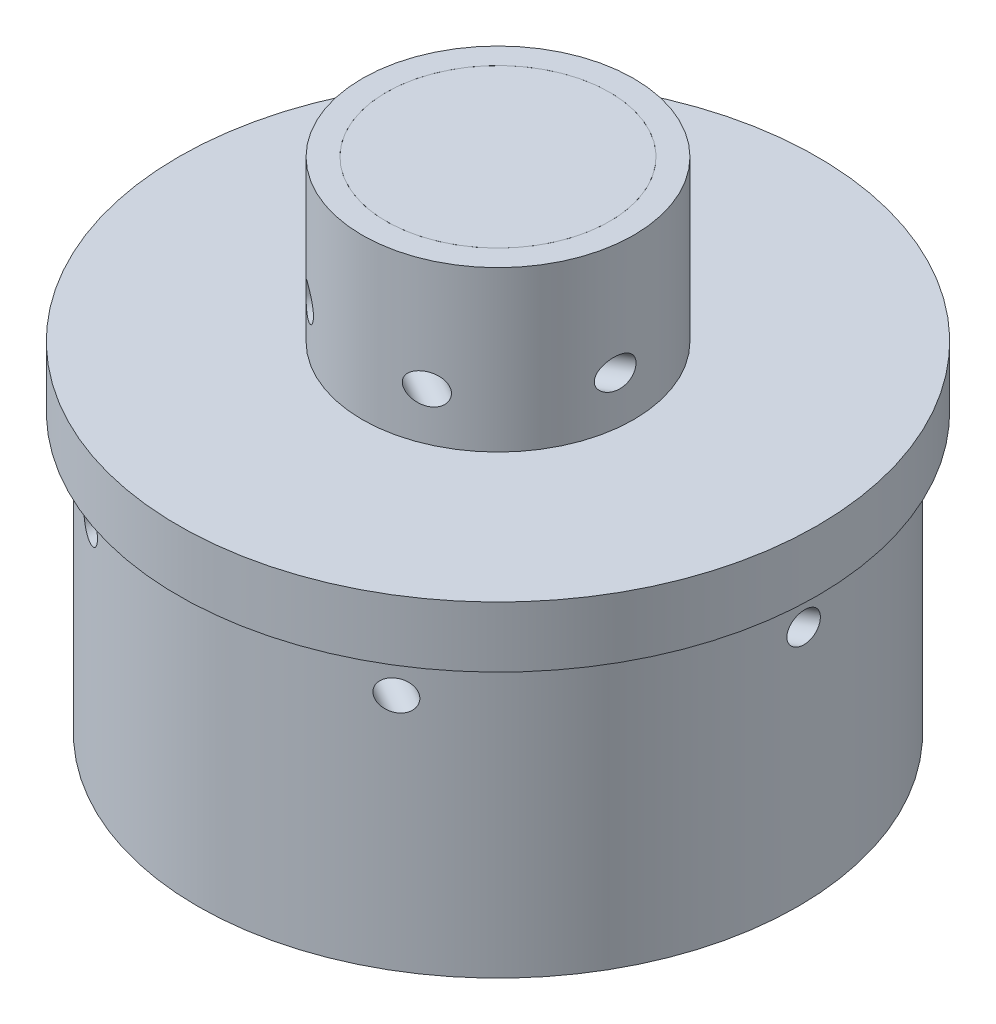
SolidWorks part; units mm, degrees
material "ASTM A36 Steel"
ref_plane "Front Plane" through (0, 0, 0) normal (0, 0, 1) x (1, 0, 0)
ref_plane "Top Plane" through (0, 0, 0) normal (0, 1, 0) x (1, 0, 0)
ref_plane "Right Plane" through (0, 0, 0) normal (1, 0, 0) x (0, 0, -1)
ref_axis "Axis1" through (0, 42.935, 0) along (0, -1, 0)
sketch "Sketch1" plane through (0, 0, 0) normal (0, 0, 1) x (1, 0, 0)
  line L1 (-5.3975, 0) -> (-5.3975, -6.35)
  line L2 (-5.3975, -6.35) -> (-12.7, -6.35)
  line L3 (-12.7, -6.35) -> (-12.7, -8.763)
  line L7 (-3.81, -3.175) -> (-3.81, -14.605)
  line L8 (-3.81, -14.605) -> (-2.54, -15.1311)
  line L9 (-2.54, -15.1311) -> (-2.54, -17.6711)
  line L10 (-2.54, -17.6711) -> (-3.3337, -17.6711)
  line L11 (-3.3337, -17.6711) -> (-3.3337, -15.6614)
  line L12 (-3.3337, -15.6614) -> (-4.6037, -15.1354)
  line L13 (-4.6037, -15.1354) -> (-4.6037, -9.525)
  line L14 (0, -1.5875) -> (0, -17.8202) construction
  line L15 (-4.6037, -9.525) -> (-6.35, -9.525)
  line L16 (-6.35, -9.525) -> (-6.35, -8.763)
  line L17 (-6.35, -8.763) -> (-12.7, -8.763)
  line L19 (-5.3975, 0) -> (-4.445, 0)
  line L20 (-4.445, 0) -> (-4.445, -3.175)
  line L21 (-4.445, -3.175) -> (-3.81, -3.175)
  point P10 (-6.35, -9.144)
  dimension "D1" = 3.81
  dimension "D2" = 2.54
  dimension "D3" = 112.5
  dimension "D4" = 11.43
  dimension "D5" = 2.54
  dimension "D6" = 1.5875
  dimension "D7" = 3.175
  dimension "D8" = 0.7937
  dimension "D9" = 0.7937
  dimension "D10" = 0.762
  dimension "D11" = 3.175
  dimension "D12" = 12.7
  dimension "D13" = 3.175
  dimension "D15" = 6.35
  dimension "D16" = 4.445
  dimension "D17" = 0.7937
revolve "Revolve1" add sketch "Sketch1" angle 360 about L14
sketch "Sketch2" plane through (0, 0, 0) normal (0, 0, 1) x (1, 0, 0)
  line L0 (-6.35, -9.525) -> (-6.35, -15.875)
  line L2 (-6.35, -15.875) -> (-4.445, -16.6641)
  line L3 (-4.445, -16.6641) -> (-4.445, -23.0141)
  line L4 (-4.445, -23.0141) -> (-6.35, -23.0141)
  line L5 (-6.35, -23.0141) -> (-6.35, -19.8391)
  line L7 (-11.938, -8.763) -> (-11.938, -19.8391)
  line L8 (-10.3886, -19.8391) -> (-11.938, -19.8391)
  line L9 (0, 42.935) -> (0, -67.065) construction
  line L10 (-6.35, -9.525) -> (-6.35, -8.763)
  line L11 (-6.35, -8.763) -> (-11.938, -8.763)
  line L13 (0, -1.5875) -> (0, -17.8202) construction
  line L14 (-6.35, -19.8391) -> (-7.3152, -19.8391)
  line L15 (-7.3152, -19.8391) -> (-7.3152, -17.8579)
  line L16 (-7.3152, -17.8579) -> (-10.3886, -17.8579)
  line L17 (-10.3886, -17.8579) -> (-10.3886, -19.8391)
  line L18 (-12.7, -6.35) -> (-12.7, -8.763) construction
  dimension "D1" = 4.445
  dimension "D2" = 3.175
  dimension "D3" = 112.5
  dimension "D4" = 6.35
  dimension "D5" = 6.35
  dimension "D6" = 6.35
  dimension "D7" = 3.0734
  dimension "D8" = 1.9812
  dimension "D9" = 10.3886
  dimension "D10" = 0.762
revolve "Revolve2" add sketch "Sketch2" angle 360 about L14
sketch "Sketch3" plane through (0, 0, 0) normal (0, 0, 1) x (1, 0, 0)
  line L0 (-4.445, -3.175) -> (0, -3.175)
  line L1 (4.445, -3.175) -> (-4.445, -3.175) construction
  line L2 (0, -3.175) -> (0, 0)
  line L3 (0, 0) -> (-4.445, 0)
  line L4 (-4.445, 0) -> (-4.445, -3.175)
revolve "Revolve3" add sketch "Sketch3" angle 360 about L2
hole_wizard "3/64 (0.04688) Diameter Hole1" positions "Sketch4" profile "Sketch5" hole size "3/64" standard "ANSI Inch"
sketch "Sketch4" plane through (0, 0, 0) normal (0, 0, 1) x (1, 0, 0)
  line L1 (-3.81, -3.175) -> (-3.81, -14.605) construction
  line L2 (4.445, 0) -> (-4.445, 0) construction
  point P0 (-3.2147, -4.445)
  dimension "D1" = 0.5953
  dimension "D2" = 4.445
sketch "Sketch5" plane through (-3.2147, -4.445, 0) normal (1, 0, 0) x (0, 1, 0)
  line L0 (0, 0) -> (0, 16.3597)
  line L1 (0, 16.3597) -> (0.5954, 16.002)
  line L2 (0.5954, 16.002) -> (0.5954, 0)
  line L5 (0.5954, 0) -> (0, 0)
  line L10 (0, 16.3597) -> (-0.5954, 16.002) construction
  line L11 (0, -6.35) -> (0, 107.95) construction
  dimension "Hole Dia." = 1.1908
  dimension "Hole Depth" = 16.002
  dimension "Drill Angle" = 118
pattern_circular "CirPattern11" count 6 over 360 about axis through (0, 42.935, 0) along (0, -1, 0) of "3/64 (0.04688) Diameter Hole1"
hole_wizard "3/64 (0.04688) Diameter Hole2" positions "Sketch6" profile "Sketch7" hole size "3/64" standard "ANSI Inch"
sketch "Sketch6" plane through (0, 0, 0) normal (0, 0, 1) x (1, 0, 0)
  line L0 (-6.35, -9.525) -> (-6.35, -8.763) construction
  line L2 (-6.35, -8.763) -> (-12.7, -8.763) construction
  point P0 (-5.7547, -10.3505)
  dimension "D1" = 0.5953
  dimension "D2" = 1.5875
sketch "Sketch7" plane through (-5.7547, -10.3505, 0) normal (1, 0, 0) x (0, 1, 0)
  line L0 (0, 0) -> (0, 16.3597)
  line L1 (0, 16.3597) -> (0.5954, 16.002)
  line L2 (0.5954, 16.002) -> (0.5954, 0)
  line L5 (0.5954, 0) -> (0, 0)
  line L10 (0, 16.3597) -> (-0.5954, 16.002) construction
  line L11 (0, -6.35) -> (0, 107.95) construction
  dimension "Hole Dia." = 1.1908
  dimension "Hole Depth" = 16.002
  dimension "Drill Angle" = 118
pattern_circular "CirPattern10" count 6 over 360 about axis through (0, 42.935, 0) along (0, -1, 0) of "3/64 (0.04688) Diameter Hole2"
